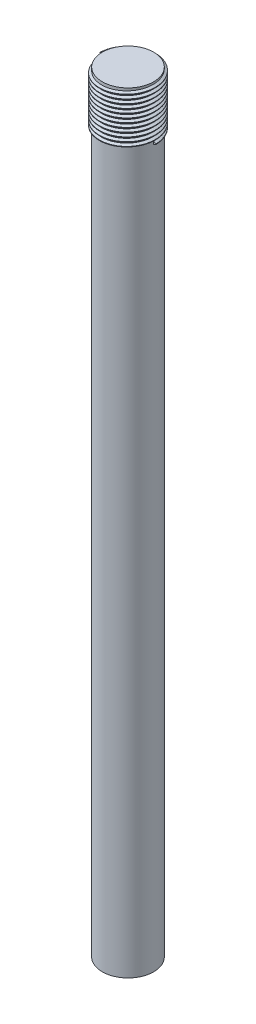
SolidWorks part; units mm, degrees
ref_plane "Alzado" through (0, 0, 0) normal (0, 0, 1) x (1, 0, 0)
ref_plane "Planta" through (0, 0, 0) normal (0, 1, 0) x (1, 0, 0)
ref_plane "Vista lateral" through (0, 0, 0) normal (1, 0, 0) x (0, 0, -1)
sketch "Croquis1" plane through (0, 0, 0) normal (0, 1, 0) x (1, 0, 0)
  circle A0 centre (0, 0) radius 5
  dimension "D1" = 10
extrude "Saliente-Extruir2" add sketch "Croquis1" along normal blind 150
sketch "Croquis3" plane through (0, 0, 0) normal (0, 1, 0) x (1, 0, 0)
  circle A0 centre (0, 0) radius 2.5
  dimension "D1" = 5
extrude "Cortar-Extruir1" cut sketch "Croquis3" along normal blind 15 contours A0
thread "Rosca1" pitch 0.8 method extrude profile "Perfil de rosca2" start angle 0, offset 0, length 10, pitch 0.8, diameter 10
ref_plane "Plano2" through (-5, 150, 0) normal (0, 0, 1) x (-1, 0, 0)
sketch "Perfil de rosca2" plane through (-5, 150, 0) normal (0, 0, 1) x (-1, 0, 0)
  line L0 (0, 0) -> (0, 0.8) construction
  line L1 (0, 0) -> (0.433, 0.25)
  line L2 (0.433, 0.25) -> (0.433, 0.35)
  line L3 (0.433, 0.35) -> (0, 0.6)
  line L4 (0.433, 0.3) -> (0, 0.3) construction
  line L11 (0, 0) -> (0, 0.6)
  point P2 (0, 0)
  dimension "Pitch" = 0.8
  dimension "Profile_Angle" = 60
  dimension "Profile_Land" = 0.1
  dimension "Profile_Height" = 0.433
